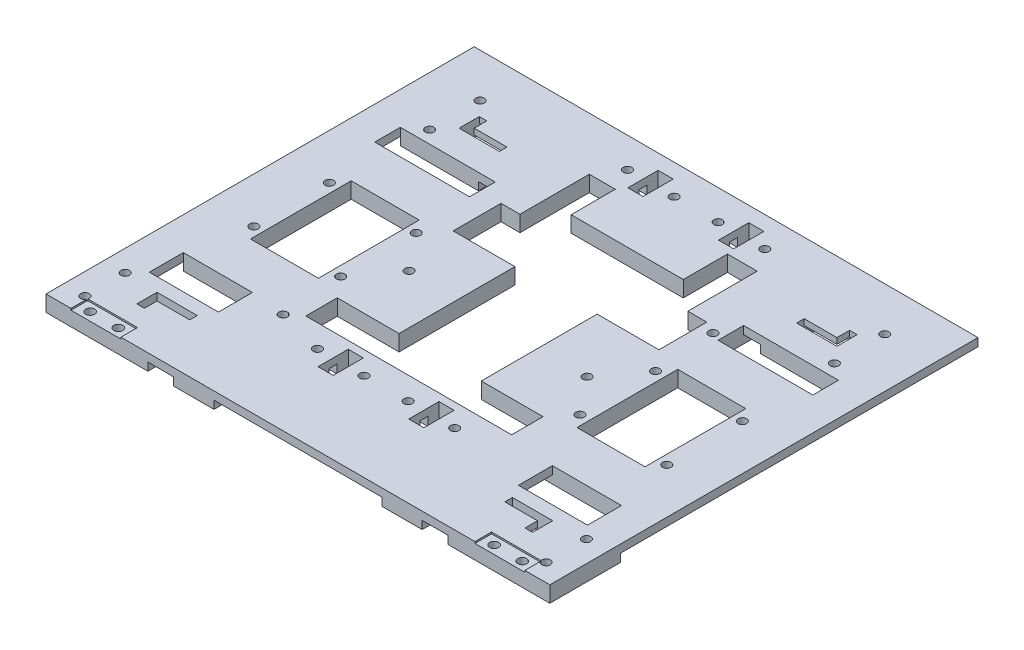
SolidWorks part; units mm, degrees
material "AISI Type A2 Tool Steel"
ref_plane "Front Plane" through (0, 0, 0) normal (0, 0, 1) x (1, 0, 0)
ref_plane "Top Plane" through (0, 0, 0) normal (0, 1, 0) x (1, 0, 0)
ref_plane "Right Plane" through (0, 0, 0) normal (1, 0, 0) x (0, 0, -1)
sketch "Sketch1" plane through (0, 0, 0) normal (0, 1, 0) x (1, 0, 0)
  line L1 (-100, -85) -> (100, -85)
  line L2 (-100, -85) -> (-100, 85)
  line L3 (-100, 85) -> (100, 85)
  line L4 (100, -85) -> (100, 85)
  line L5 (-100, -85) -> (100, 85) construction
  line L6 (-100, 85) -> (100, -85) construction
  point P0 (0, 0)
  dimension "D1" = 200
  dimension "D2" = 170
extrude "1/4\" Steel Plate" add sketch "Sketch1" along normal blind 6.35
ref_plane "Midplane" through (0, 0, 0) normal (-1, 0, 0) x (0, 0, 1)
sketch "Sketch2" plane through (0, 6.35, 0) normal (0, 1, 0) x (1, 0, 0)
  line L0 (-100, -85) -> (100, -85) construction
  line L1 (-90.094, -85) -> (-70.282, -85)
  line L2 (-90.094, -85) -> (-90.094, -78.396)
  line L3 (-90.094, -78.396) -> (-70.282, -78.396)
  line L4 (-70.282, -85) -> (-70.282, -78.396)
  line L5 (-100, 85) -> (-100, -85) construction
  dimension "D1" = 9.906
  dimension "D2" = 6.604
  dimension "D3" = 19.812
extrude "BladeHingeCut" cut sketch "Sketch2" against normal blind 0.635
hole_wizard "BladeHingeHole" positions "3DSketch2" profile "Sketch4" hole size "#8" standard "ANSI Inch" end condition through all
sketch3d "3DSketch2"
  line L0 (-90.094, 5.715, 85) -> (-70.282, 5.715, 85) construction
  line L10 (-80.188, 5.715, 78.396) -> (-80.188, 5.715, 85) construction
  line L11 (-70.282, 5.715, 78.396) -> (-90.094, 5.715, 78.396) construction
  point P0 (-74.6, 5.715, 81.698)
  point P2 (-85.776, 5.715, 81.698)
  dimension "D1" = 3.302
  dimension "D2" = 3.302
  dimension "D3" = 11.176
  dimension "D4" = 5.588
sketch "Sketch4" plane through (-74.6, 5.715, 81.698) normal (1, 0, 0) x (0, 0, 1)
  line L0 (0, 0) -> (0, 5.715)
  line L1 (0, 5.715) -> (1.778, 5.715)
  line L2 (1.778, 5.715) -> (1.778, 0)
  line L5 (1.778, 0) -> (0, 0)
  line L11 (0, -6.35) -> (0, 107.95) construction
  dimension "Thru Hole Dia." = 3.556
  dimension "Thru Hole Depth" = 5.715
sketch "Sketch5" plane through (0, 0, 0) normal (0, -1, 0) x (1, 0, 0)
  line L1 (-88.301, 79.173) -> (-83.251, 79.173)
  line L2 (-88.301, 79.173) -> (-88.301, 84.223)
  line L3 (-88.301, 84.223) -> (-83.251, 84.223)
  line L4 (-83.251, 79.173) -> (-83.251, 84.223)
  line L5 (-88.301, 79.173) -> (-83.251, 84.223) construction
  line L6 (-88.301, 84.223) -> (-83.251, 79.173) construction
  line L7 (-72.075, 79.173) -> (-77.125, 79.173)
  line L8 (-72.075, 79.173) -> (-72.075, 84.223)
  line L9 (-72.075, 84.223) -> (-77.125, 84.223)
  line L10 (-77.125, 79.173) -> (-77.125, 84.223)
  line L11 (-72.075, 79.173) -> (-77.125, 84.223) construction
  line L12 (-72.075, 84.223) -> (-77.125, 79.173) construction
  point P0 (-85.776, 81.698)
  point P6 (-74.6, 81.698)
  dimension "D1" = 5.05
  dimension "D2" = 5.05
  dimension "D3" = 5.05
  dimension "D4" = 5.05
extrude "BladeNutCut" cut sketch "Sketch5" against normal blind 2
mirror "BladeHingeMirror" about plane through (0, 0, 0) normal (-1, 0, 0) of "BladeNutCut", "BladeHingeHole", "BladeHingeCut"
sketch "Sketch6" plane through (0, 0, 0) normal (0, -1, 0) x (-1, 0, 0)
  line L0 (77.3259, -27.4233) -> (77.3259, 16.3767) construction
  line L1 (78.3259, 14.4767) -> (51.3259, 14.4767)
  line L2 (78.3259, 14.4767) -> (78.3259, -25.5233)
  line L3 (78.3259, -25.5233) -> (51.3259, -25.5233)
  line L4 (51.3259, 14.4767) -> (51.3259, -25.5233)
  line L5 (57.3259, 16.3767) -> (57.3259, -27.4233) construction
  point P6 (78.3259, -5.5233)
  dimension "D1" = 1
  dimension "D2" = 20
  dimension "D3" = 6
  dimension "D4" = 20
extrude "Cut-Extrude1" cut sketch "Sketch6" against normal up to surface (6.35 mm away) up to face at (0, 6.35, 54.4653)
sketch "Sketch7" plane through (0, 0, 0) normal (0, -1, 0) x (-1, 0, 0)
  line L0 (51.3259, -25.5233) -> (78.3259, -25.5233) construction
  line L1 (79.3259, -30.5233) -> (49.3259, -30.5233)
  line L2 (79.3259, -30.5233) -> (79.3259, -40.5233)
  line L3 (79.3259, -40.5233) -> (49.3259, -40.5233)
  line L4 (49.3259, -30.5233) -> (49.3259, -40.5233)
  line L5 (80.3259, 19.4767) -> (50.3259, 19.4767)
  line L6 (80.3259, 19.4767) -> (80.3259, 29.4767)
  line L7 (80.3259, 29.4767) -> (50.3259, 29.4767)
  line L8 (50.3259, 19.4767) -> (50.3259, 29.4767)
  line L9 (29.3259, -25.5233) -> (19.3259, -25.5233)
  line L10 (29.3259, -25.5233) -> (29.3259, 14.4767)
  line L11 (29.3259, 14.4767) -> (19.3259, 14.4767)
  line L12 (19.3259, -25.5233) -> (19.3259, 14.4767)
  line L17 (78.3259, -25.5233) -> (78.3259, 14.4767) construction
  line L18 (78.3259, 14.4767) -> (51.3259, 14.4767) construction
  line L19 (51.3259, 14.4767) -> (51.3259, -25.5233) construction
  line L29 (46.3259, -80.5233) -> (36.3259, -80.5233)
  line L30 (46.3259, -80.5233) -> (46.3259, -50.5233)
  line L31 (46.3259, -50.5233) -> (36.3259, -50.5233)
  line L32 (36.3259, -80.5233) -> (36.3259, -50.5233)
  line L33 (20, -70.5233) -> (-20, -70.5233)
  line L34 (20, -70.5233) -> (20, -60.5233)
  line L35 (20, -60.5233) -> (-20, -60.5233)
  line L36 (-20, -70.5233) -> (-20, -60.5233)
  line L37 (-100, 85) -> (100, 85) construction
  line L38 (36.3259, 39.4767) -> (46.3259, 39.4767)
  line L39 (36.3259, 39.4767) -> (36.3259, 69.4767)
  line L40 (36.3259, 69.4767) -> (46.3259, 69.4767)
  line L41 (46.3259, 39.4767) -> (46.3259, 69.4767)
  line L42 (20, 49.4767) -> (-20, 49.4767)
  line L43 (20, 49.4767) -> (20, 59.4767)
  line L44 (20, 59.4767) -> (-20, 59.4767)
  line L45 (-20, 49.4767) -> (-20, 59.4767)
  point P18 (0, 49.4767)
  point P55 (20, 54.4767)
  point P56 (36.3259, 54.4767)
  point P57 (20, -65.5233)
  point P58 (36.3259, -65.5233)
  point P60 (0, 85)
  dimension "D1" = 5
  dimension "D2" = 30
  dimension "D3" = 10
  dimension "D4" = 1
  dimension "D5" = 5
  dimension "D6" = 1
  dimension "D7" = 10
  dimension "D8" = 30
  dimension "D9" = 40
  dimension "D10" = 10
  dimension "D11" = 22
  dimension "D14" = 10
  dimension "D17" = 5
  dimension "D18" = 40
  dimension "D19" = 10
  dimension "D20" = 30
  dimension "D21" = 25
  dimension "D22" = 10
  dimension "D23" = 30
  dimension "D24" = 25
  dimension "D25" = 10
  dimension "D26" = 40
other "AlignGroup1"
extrude "Cut-Extrude2" cut sketch "Sketch7" against normal blind 5 contours L30 L29 L32 L31 | L34 L33 L36 L35 | L10 L9 L12 L11 | L2 L1 L4 L3 | L6 L5 L8 L7 | L39 L38 L41 L40 | L43 L42 L45 L44
sketch "Sketch8" plane through (0, 6.35, 0) normal (0, 1, 0) x (1, 0, 0)
  line L0 (-83.5459, -55) -> (-83.5459, -85) construction
  line L1 (-78.5459, -62.396) -> (-62.5459, -62.396)
  line L2 (-78.5459, -62.396) -> (-78.5459, -73.396)
  line L3 (-78.5459, -73.396) -> (-62.5459, -73.396)
  line L4 (-62.5459, -62.396) -> (-62.5459, -73.396)
  line L5 (-70.282, -78.396) -> (-90.094, -78.396) construction
  dimension "D1" = 11
  dimension "D2" = 16
  dimension "D3" = 5
  dimension "D4" = 5
extrude "Cut-Extrude3" cut sketch "Sketch8" along normal blind 4 from surface starting at face at (0, 0, -54.4767)
sketch "Sketch9" plane through (0, 4, 0) normal (0, -1, 0) x (1, 0, 0)
  line L0 (-78.5459, 62.396) -> (-62.5459, 62.396)
  line L9 (-78.5459, 62.396) -> (-78.5459, 70.396)
  line L10 (-78.5459, 73.396) -> (-78.5459, 62.396) construction
  line L11 (-78.5459, 70.396) -> (-75.5459, 70.396)
  line L12 (-75.5459, 70.396) -> (-75.5459, 65.396)
  line L13 (-75.5459, 65.396) -> (-62.5459, 65.396)
  line L14 (-62.5459, 62.396) -> (-62.5459, 73.396) construction
  line L15 (-62.5459, 65.396) -> (-62.5459, 62.396)
  dimension "D1" = 8
  dimension "D2" = 3
  dimension "D3" = 3
extrude "Cut-Extrude4" cut sketch "Sketch9" against normal up to surface (2.35 mm away) contours L13 L15 L0 L9 L11 L12 up to face at (-64.8259, 6.35, 5.5233)
sketch "Sketch10" plane through (0, 0, 0) normal (0, -1, 0) x (-1, 0, 0)
  line L1 (75, 65) -> (59, 65)
  line L2 (75, 65) -> (75, 54)
  line L3 (75, 54) -> (59, 54)
  line L4 (59, 65) -> (59, 54)
  line L6 (100, 85) -> (100, -85) construction
  line L7 (-100, 85) -> (100, 85) construction
  dimension "D1" = 11
  dimension "D2" = 16
  dimension "D3" = 25
  dimension "D4" = 20
extrude "Cut-Extrude5" cut sketch "Sketch10" against normal blind 4
sketch "Sketch11" plane through (0, 4, 0) normal (0, -1, 0) x (1, 0, 0)
  line L0 (-59, -54) -> (-75, -54)
  line L1 (-75, -54) -> (-75, -62)
  line L2 (-75, -54) -> (-75, -65) construction
  line L3 (-75, -62) -> (-72, -62)
  line L4 (-72, -62) -> (-72, -57)
  line L5 (-72, -57) -> (-59, -57)
  line L6 (-59, -65) -> (-59, -54) construction
  line L7 (-59, -57) -> (-59, -54)
  dimension "D1" = 3
  dimension "D2" = 3
  dimension "D3" = 8
extrude "Cut-Extrude6" cut sketch "Sketch11" against normal up to next
mirror "Mirror2" about plane through (0, 0, 0) normal (-1, 0, 0) of "Cut-Extrude6", "Cut-Extrude5", "Cut-Extrude4", "Cut-Extrude3", "Cut-Extrude2", "Cut-Extrude1"
hole_wizard "CSK for M3 Flat Head Machine Screw1" positions "Sketch12" profile "Sketch13" countersink size "M3" standard "ANSI Metric"
sketch "Sketch12" plane through (0, 0, 0) normal (0, -1, 0) x (-1, 0, 0)
  point P0 (-91.5503, -78)
  point P2 (-91.5503, -62)
  point P4 (-80.3371, 47.6378)
  point P7 (-80.3371, 67.6378)
  point P10 (-35.8509, -6.0466)
  point P13 (-45.8509, 33.9534)
  point P16 (35.8509, -5)
  point P19 (45.8509, -45)
  point P22 (91.5459, -62)
  point P25 (91.5459, -78)
  point P28 (80.3371, 47.6378)
  point P31 (80.3371, 67.6378)
  point P39 (-81.9659, -20.5233)
  point P42 (-81.9659, 9.4767)
  point P45 (-47.5109, -20.5233)
  point P48 (-47.5109, 9.4767)
  point P51 (47.5109, -20.5233)
  point P54 (81.9659, -20.5233)
  point P57 (81.9659, 9.4767)
  point P60 (47.5109, 9.4767)
sketch "Sketch13" plane through (91.5503, 0, 78) normal (1, 0, 0) x (0, 0, -1)
  line L0 (0, 0) -> (0, 14)
  line L1 (0, 14) -> (1.7, 14)
  line L2 (1.7, 14) -> (1.7, 1.45)
  line L3 (1.7, 1.45) -> (3.15, 0)
  line L5 (3.15, 0) -> (0, 0)
  line L6 (-1.7, 1.45) -> (-3.15, 0) construction
  line L10 (0, 14) -> (-1.7, 14) construction
  line L11 (0, -6.35) -> (0, 107.95) construction
  dimension "Hole Dia." = 3.4
  dimension "Hole Depth" = 14
  dimension "Near C'Sink Dia." = 6.3
  dimension "Near C'Sink Angle" = 90
  dimension "Drill Angle" = 180
sketch "Sketch14" plane through (0, 0, 0) normal (0, -1, 0) x (1, 0, 0)
  line L0 (0, -7.6262) -> (0, -14.6112) construction
  line L1 (21, 56) -> (15, 56)
  line L2 (21, 56) -> (21, 44)
  line L3 (21, 44) -> (15, 44)
  line L4 (15, 56) -> (15, 44)
  line L6 (-100, 85) -> (100, 85) construction
  point P6 (15, 50)
  dimension "D1" = 6
  dimension "D2" = 12
  dimension "D3" = 15
  dimension "D4" = 35
extrude "Cut-Extrude7" cut sketch "Sketch14" against normal blind 10
sketch "Sketch15" plane through (0, 0, 0) normal (0, -1, 0) x (1, 0, 0)
  line L1 (10.75, 48.4) -> (25.25, 48.4)
  line L2 (10.75, 48.4) -> (10.75, 51.6)
  line L3 (10.75, 51.6) -> (25.25, 51.6)
  line L4 (25.25, 48.4) -> (25.25, 51.6)
  line L5 (15, 56) -> (15, 44) construction
  line L6 (15, 44) -> (21, 44) construction
  point P6 (18, 44)
  point P9 (15, 50)
  point P10 (10.75, 50)
  point P11 (18, 48.4)
  dimension "D2" = 14.5
  dimension "D3" = 3.2
extrude "Cut-Extrude8" cut sketch "Sketch15" against normal blind 3.5
sketch "Sketch16" plane through (0, 0, 0) normal (0, -1, 0) x (1, 0, 0)
  line L0 (15, 44) -> (21, 44) construction
  line L1 (15, -79) -> (21, -79)
  line L2 (15, -79) -> (15, -67)
  line L3 (15, -67) -> (21, -67)
  line L4 (21, -79) -> (21, -67)
  line L5 (100, -85) -> (-100, -85) construction
  point P6 (18, 44)
  point P7 (18, -67)
  point P8 (15, -73)
  dimension "D1" = 12
  dimension "D2" = 6
  dimension "D3" = 12
extrude "Cut-Extrude9" cut sketch "Sketch16" against normal through all
sketch "Sketch17" plane through (0, 0, 0) normal (0, -1, 0) x (1, 0, 0)
  line L1 (10.75, -74.6) -> (25.25, -74.6)
  line L2 (10.75, -74.6) -> (10.75, -71.4)
  line L3 (10.75, -71.4) -> (25.25, -71.4)
  line L4 (25.25, -74.6) -> (25.25, -71.4)
  line L8 (21, -67) -> (15, -67) construction
  line L9 (15, -67) -> (15, -79) construction
  point P6 (15, -73)
  point P7 (10.75, -73)
  point P14 (18, -67)
  point P15 (18, -71.4)
  dimension "D1" = 14.5
  dimension "D2" = 3.2
extrude "Cut-Extrude10" cut sketch "Sketch17" against normal blind 3.5
hole_wizard "CSK for M3 Flat Head Machine Screw2" positions "Sketch18" profile "Sketch19" countersink size "M3" standard "ANSI Metric"
sketch "Sketch18" plane through (0, 0, 0) normal (0, -1, 0) x (-1, 0, 0)
  line L0 (-36.6491, -50) -> (24.8009, -50) construction
  line L2 (-21, 74.6) -> (-25.25, 74.6) construction
  line L4 (-10.75, 74.6) -> (-15, 74.6) construction
  line L5 (-25.25, 74.6) -> (-25.25, 71.4) construction
  line L6 (-10.75, 71.4) -> (-10.75, 74.6) construction
  point P0 (-8.75, -50)
  point P4 (-27.25, -50)
  point P6 (-8.75, 73.1)
  point P8 (-27.25, 73.1)
  dimension "D1" = 1.5
  dimension "D2" = 1.5
  dimension "D3" = 2
  dimension "D4" = 2
sketch "Sketch19" plane through (8.75, 0, 50) normal (1, 0, 0) x (0, 0, -1)
  line L0 (0, 0) -> (0, 11.0215)
  line L1 (0, 11.0215) -> (1.7, 10)
  line L2 (1.7, 10) -> (1.7, 1.45)
  line L3 (1.7, 1.45) -> (3.15, 0)
  line L5 (3.15, 0) -> (0, 0)
  line L6 (-1.7, 1.45) -> (-3.15, 0) construction
  line L10 (0, 11.0215) -> (-1.7, 10) construction
  line L11 (0, -6.35) -> (0, 107.95) construction
  dimension "Hole Dia." = 3.4
  dimension "Hole Depth" = 10
  dimension "Near C'Sink Dia." = 6.3
  dimension "Near C'Sink Angle" = 90
  dimension "Drill Angle" = 118
mirror "Mirror3" about plane through (0, 0, 0) normal (-1, 0, 0) of "Cut-Extrude7", "Cut-Extrude8", "Cut-Extrude9", "Cut-Extrude10", "CSK for M3 Flat Head Machine Screw2"
sketch "Sketch20" plane through (0, 0, 0) normal (0, -1, 0) x (1, 0, 0)
  line L0 (-100, 85) -> (100, 85) construction
  line L1 (-59.5459, 85) -> (-49.3259, 85)
  line L2 (-59.5459, 85) -> (-59.5459, 57)
  line L3 (-50.8509, 50) -> (-49.3259, 50)
  line L4 (-49.3259, 85) -> (-49.3259, 50)
  line L5 (-100, -85) -> (-100, 85) construction
  line L6 (-100, 57) -> (-59.5459, 57)
  line L7 (-100, 57) -> (-100, 45.2891)
  line L8 (-86.9659, 43.5233) -> (-50.8509, 43.5233)
  line L9 (-50.8509, 50) -> (-50.8509, 43.5233)
  line L10 (100, -85) -> (-100, -85) construction
  line L12 (-86.9659, 43.5233) -> (-86.9659, -32.4767)
  line L13 (-89.1269, -85) -> (-100, -85)
  line L14 (-100, 45.2891) -> (-100, -85)
  line L15 (-86.9659, -32.4767) -> (-49.3259, -32.4767)
  line L17 (-86.9659, -42.6378) -> (-56, -42.6378)
  line L18 (-49.3259, -35.2903) -> (-49.3259, -42.3731)
  line L19 (-86.9659, -72.4767) -> (-56, -72.4767)
  line L21 (-89.1269, -85) -> (-46.8803, -85)
  line L23 (-86.9659, -42.6378) -> (-86.9659, -72.4767)
  line L25 (-56, -42.6378) -> (-56, -72.4767)
  line L27 (-49.3259, -42.3731) -> (-49.3259, -72.4767)
  line L28 (-40.8509, -17.4767) -> (-20.1564, -17.4767)
  line L29 (-40.8509, -17.4767) -> (-40.8509, -31.3828)
  line L30 (-40.8509, -36.4767) -> (-33.3259, -36.4767)
  line L33 (-33.3259, -36.4767) -> (-33.3259, -64)
  line L34 (-33.3259, -64) -> (-23, -64)
  line L35 (-23, -46.4767) -> (-23, -64)
  line L36 (-44.7194, -72.4767) -> (-32.25, -72.4767)
  line L38 (-46.8803, -85) -> (-32.25, -85)
  line L39 (-32.25, -72.4767) -> (-32.25, -85)
  line L40 (-40.8509, 41) -> (-20.1564, 41)
  line L41 (-40.8509, 41) -> (-40.8509, 28.5233)
  line L42 (-40.8509, 28.5233) -> (-20.1564, 28.5233)
  line L44 (-33.3259, 85) -> (-23, 85)
  line L45 (-33.3259, 85) -> (-33.3259, 59)
  line L46 (-33.3259, 59) -> (-23, 59)
  line L47 (-23, 85) -> (-23, 59)
  line L48 (0, 41) -> (-15.9718, 41)
  line L49 (0, 41) -> (0, -46.4767)
  line L50 (0, -46.4767) -> (-15.9718, -46.4767)
  line L51 (-16.3259, 28.5233) -> (-16.3259, -17.4767)
  line L52 (-49.3259, -72.4767) -> (-44.7194, -72.4767)
  line L54 (-40.8509, -31.3828) -> (-40.8509, -36.4767)
  line L55 (-20.1564, 41) -> (-15.9718, 41)
  line L57 (-20.1564, 28.5233) -> (-16.3259, 28.5233)
  line L59 (-20.1564, -17.4767) -> (-16.3259, -17.4767)
  line L61 (-20.1564, -46.4767) -> (-15.9718, -46.4767)
  line L65 (-23, -46.4767) -> (-20.1564, -46.4767)
  line L71 (-49.3259, -32.4767) -> (-49.3259, -35.2903)
  line L72 (-46.3259, -39.4767) -> (-46.3259, -69.4767) construction
  line L73 (-80.3259, -29.4767) -> (-50.3259, -29.4767) construction
  line L74 (-79.3259, 40.5233) -> (-49.3259, 40.5233) construction
  line L75 (-46.3259, 80.5233) -> (-46.3259, 50.5233) construction
  line L76 (-62.5459, 65.396) -> (-62.5459, 73.396) construction
  line L77 (-36.3259, 80.5233) -> (-36.3259, 50.5233) construction
  line L78 (-20, 70.5233) -> (-20, 60.5233) construction
  line L79 (-21, 56) -> (-15, 56) construction
  line L80 (-15, 44) -> (-21, 44) construction
  line L81 (-29.3259, 25.5233) -> (-19.3259, 25.5233) construction
  line L82 (-19.3259, 25.5233) -> (-19.3259, -14.4767) construction
  line L83 (-29.3259, -14.4767) -> (-19.3259, -14.4767) construction
  line L84 (-20, -49.4767) -> (20, -49.4767) construction
  line L85 (-20, -49.4767) -> (-20, -59.4767) construction
  line L86 (-36.3259, -39.4767) -> (-36.3259, -69.4767) construction
  line L87 (-36.3259, -39.4767) -> (-46.3259, -39.4767) construction
  line L88 (-21, -67) -> (-15, -67) construction
  line L89 (-36.3259, -69.4767) -> (-46.3259, -69.4767) construction
  line L90 (-59, -65) -> (-59, -54) construction
  line L91 (0, 3.4925) -> (0, -3.4925) construction
  line L92 (-20, 70.5233) -> (20, 70.5233) construction
  line L93 (-23, 85) -> (0, 85)
  line L94 (-23, 85) -> (-23, 73.5233)
  line L95 (-23, 73.5233) -> (0, 73.5233)
  line L96 (0, 85) -> (0, 73.5233)
  circle A0 centre (-45.8509, 45) radius 1.7 construction
  circle A1 centre (-81.9659, 20.5233) radius 1.7 construction
  circle A2 centre (-91.5459, 62) radius 1.7 construction
  circle A3 centre (-27.25, -73.1) radius 1.7 construction
  circle A4 centre (-80.3371, -47.6378) radius 1.7 construction
  dimension "D1" = 5
  dimension "D10" = 5
  dimension "D2" = 3
  dimension "D3" = 3
  dimension "D4" = 5
  dimension "D5" = 3
  dimension "D6" = 5
  dimension "D7" = 5
  dimension "D8" = 3
  dimension "D9" = 3
  dimension "D11" = 3
  dimension "D12" = 3
  dimension "D13" = 3
  dimension "D14" = 3
  dimension "D15" = 3
  dimension "D16" = 5
  dimension "D17" = 3
  dimension "D18" = 3
  dimension "D19" = 3
  dimension "D20" = 3
  dimension "D21" = 3
  dimension "D22" = 3
  dimension "D23" = 3
  dimension "D24" = 3
  dimension "D25" = 5
  dimension "D26" = 5
  dimension "D27" = 3
  dimension "D28" = 3
extrude "Cut-Extrude11" cut sketch "Sketch20" against normal blind 3.175 contours L47 L44 L45 L46 | L35 L65 L61 L50 L49 L48 L55 L40 L41 L42 L57 L51 L59 L28 L29 L54 L30 L33 L34 | L71 L15 L12 L8 L9 L3 L4 L1 L2 L6 L7 L14 L13 L21 L38 L39 L36 L52 L27 L18 L17 L25 L19 L23 | L94 L93 L96 L95 region at (-54.4359, 0, 83.17) region at (-30.5037, 0, -18.6034) region at (-28.163, 0, 72)
mirror "Mirror4" about plane through (0, 0, 0) normal (-1, 0, 0) of "Cut-Extrude11"
sketch "Sketch21" plane through (0, 0, 0) normal (0, -1, 0) x (1, 0, 0)
  line L0 (40.8509, -17.4767) -> (16.3259, -17.4767) construction
  line L1 (-40.8509, 41) -> (40.8509, 41)
  line L2 (-40.8509, 41) -> (-40.8509, 28.5233)
  line L3 (-40.8509, 28.5233) -> (40.8509, 28.5233)
  line L4 (40.8509, 41) -> (40.8509, 28.5233)
  line L5 (-16.3259, 28.5233) -> (16.3259, 28.5233)
  line L6 (-16.3259, 28.5233) -> (-16.3259, -17.4767)
  line L7 (-16.3259, -17.4767) -> (16.3259, -17.4767)
  line L8 (16.3259, 28.5233) -> (16.3259, -17.4767)
  line L9 (-23, -46.4767) -> (21.5374, -46.4767)
  line L10 (-23, -46.4767) -> (-23, -17.4767)
  line L11 (-23, -17.4767) -> (21.5374, -17.4767)
  line L12 (21.5374, -46.4767) -> (21.5374, -17.4767)
  line L13 (-59.5459, 85) -> (-59.5459, 57) construction
  line L14 (-33.3259, -64) -> (-23, -64)
  line L15 (-33.3259, -64) -> (-33.3259, -17.4767)
  line L16 (-33.3259, -17.4767) -> (-23, -17.4767)
  line L17 (-23, -64) -> (-23, -17.4767)
  line L18 (33.3259, -64) -> (21.5374, -64)
  line L19 (33.3259, -64) -> (33.3259, -17.4767)
  line L20 (33.3259, -17.4767) -> (21.5374, -17.4767)
  line L21 (21.5374, -64) -> (21.5374, -17.4767)
  line L22 (-40.8509, -17.4767) -> (40.8509, -17.4767)
  line L23 (-40.8509, -17.4767) -> (-40.8509, -36.4767)
  line L24 (-40.8509, -36.4767) -> (40.8509, -36.4767)
  line L25 (40.8509, -17.4767) -> (40.8509, -36.4767)
  line L26 (-49.3259, -32.4767) -> (-86.9659, -32.4767)
  line L27 (-49.3259, -32.4767) -> (-49.3259, -42.6378)
  line L28 (-49.3259, -42.6378) -> (-86.9659, -42.6378)
  line L29 (-86.9659, -32.4767) -> (-86.9659, -42.6378)
  line L30 (86.9659, -42.6378) -> (49.3259, -42.6378)
  line L31 (86.9659, -42.6378) -> (86.9659, -32.4767)
  line L32 (86.9659, -32.4767) -> (49.3259, -32.4767)
  line L33 (49.3259, -42.6378) -> (49.3259, -32.4767)
  line L34 (-86.9659, 43.5233) -> (-59.5459, 43.5233)
  line L35 (-86.9659, 43.5233) -> (-86.9659, 57)
  line L36 (-86.9659, 57) -> (-59.5459, 57)
  line L37 (-59.5459, 43.5233) -> (-59.5459, 57)
  line L39 (59.5459, 57) -> (86.9659, 57)
  line L40 (59.5459, 57) -> (59.5459, 43.5233)
  line L41 (59.5459, 43.5233) -> (86.9659, 43.5233)
  line L42 (86.9659, 57) -> (86.9659, 43.5233)
extrude "Cut-Extrude12" cut sketch "Sketch21" against normal up to surface (6.35 mm away) contours L14 L17 L10 L16 L15 | L9 L12 L11 L7 L10 | L21 L18 L19 L20 L12 | L8 L3 L6 L7 | L4 L1 L2 L3 | L15 L14 L17 L16 | L10 L9 L12 L11 | L23 L22 L25 L24 | L31 L30 L33 L32 | L40 L39 L42 L41 | L35 L34 L37 L36 | L27 L26 L29 L28 region at (0, 0, 34.7616) region at (0, 0, 5.5233) region at (-0.7313, 0, -26.9767) region at (-28.163, 0, -50.2384) region at (27.4317, 0, -50.2384) up to face at (-8.75, 6.35, 48.3)
